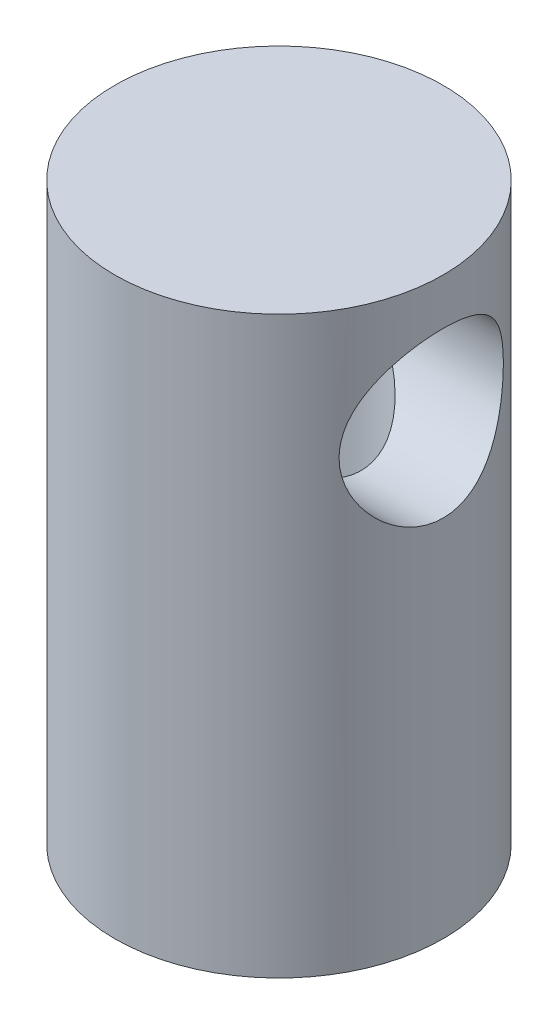
SolidWorks part; units mm, degrees
material "不锈钢 (铁素体)"
ref_plane "前视基准面" through (0, 0, 0) normal (0, 0, 1) x (1, 0, 0)
ref_plane "上视基准面" through (0, 0, 0) normal (0, 1, 0) x (1, 0, 0)
ref_plane "右视基准面" through (0, 0, 0) normal (1, 0, 0) x (0, 0, -1)
other "Configuration Table"
sketch "草图1" plane through (0, 0, 0) normal (0, 1, 0) x (1, 0, 0)
  circle A0 centre (0, 0) radius 6
extrude "凸台-拉伸2" add sketch "草图1" along normal blind 21
sketch "草图2" plane through (0, 0, 0) normal (0, -1, 0) x (1, 0, 0)
  circle A0 centre (0, 0) radius 3
extrude "切除-拉伸1" cut sketch "草图2" against normal blind 15
sketch "草图3" plane through (0, 0, 0) normal (1, 0, 0) x (0, 0, -1)
  circle A0 centre (0, 16.3094) radius 3
extrude "切除-拉伸2" cut sketch "草图3" against normal blind 10 and the other way blind 10
